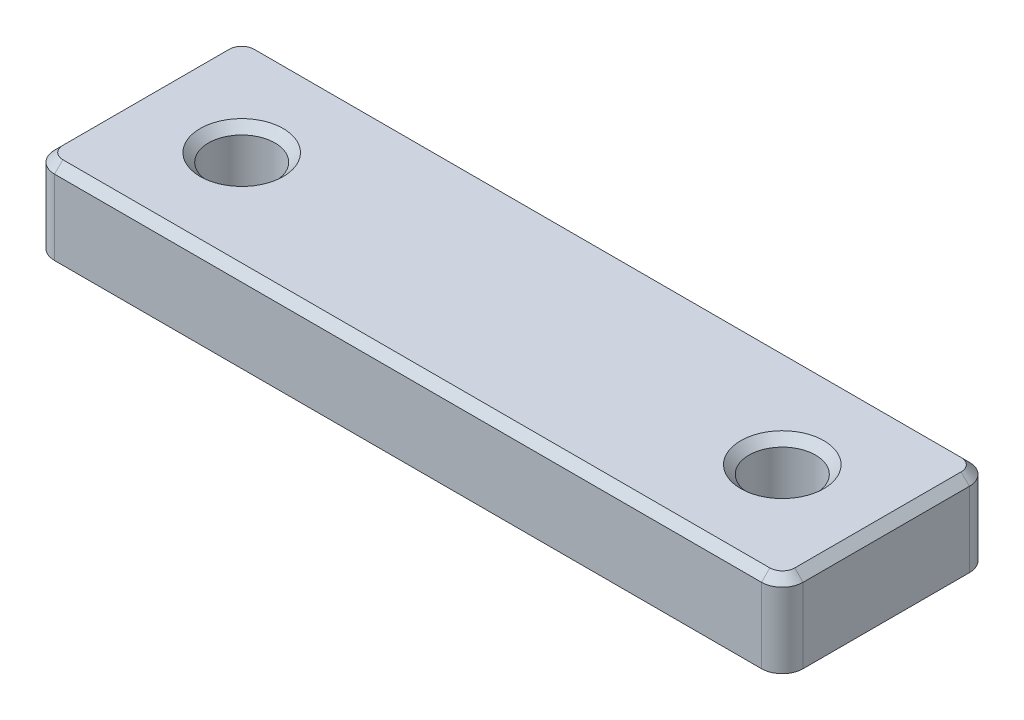
SolidWorks part; units mm, degrees
ref_plane "前视基准面" through (0, 0, 0) normal (0, 0, 1) x (1, 0, 0)
ref_plane "上视基准面" through (0, 0, 0) normal (0, 1, 0) x (1, 0, 0)
ref_plane "右视基准面" through (0, 0, 0) normal (1, 0, 0) x (0, 0, -1)
other "Configuration Table"
sketch "草图1" plane through (0, 0, 0) normal (0, 1, 0) x (1, 0, 0)
  line L1 (0, 0) -> (36, 0)
  line L2 (0, 0) -> (0, -10)
  line L3 (0, -10) -> (36, -10)
  line L4 (36, 0) -> (36, -10)
  circle A0 centre (5, -5) radius 1.6
  circle A1 centre (31, -5) radius 1.6
  point P9 (18, 0)
  point P10 (0, -5)
  point P11 (17.8792, 0)
  dimension "D3" = 3.2
  dimension "D4" = 3.2
  dimension "D1" = 36
  dimension "D2" = 10
  dimension "D5" = 26
  dimension "D6" = 13
  dimension "D7" = 0
extrude "凸台-拉伸1" add sketch "草图1" along normal blind 4
fillet "圆角1" radius 1 4 edges at (0, 2, 0) (36, 2, 0) (36, 2, 10) (0, 2, 10)
chamfer "倒角1" distance 0.4 angle 45 10 edges at (31, 4, 6.6) (18, 4, 0) (36, 4, 5) (18, 4, 10) (0, 4, 5) (5, 4, 6.6) (35.7071, 4, 0.2929) (35.7071, 4, 9.7071) (0.2929, 4, 9.7071) (0.2929, 4, 0.2929)
